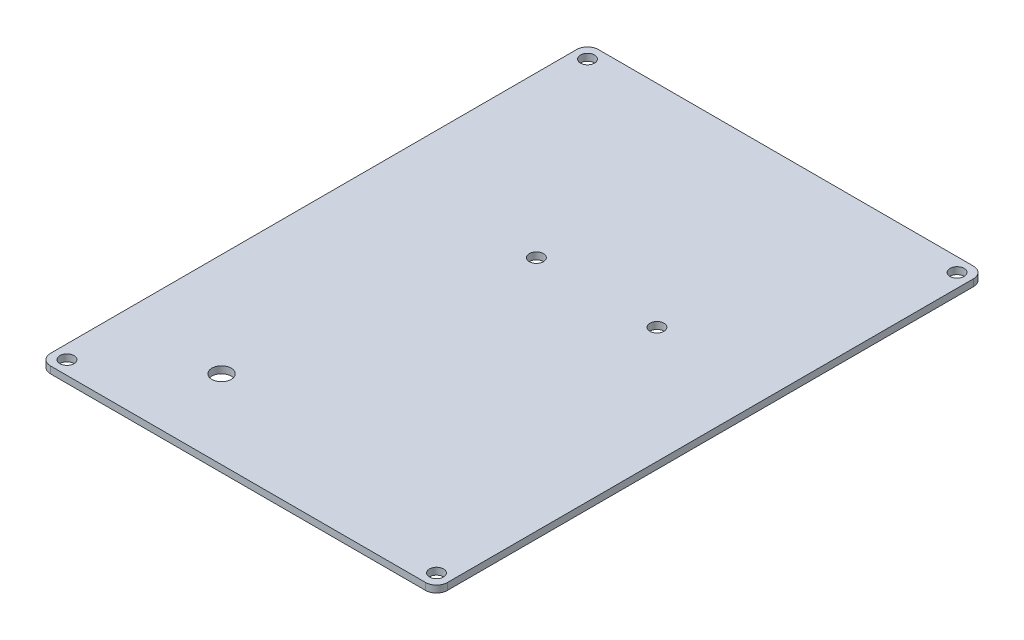
SolidWorks part; units mm, degrees
ref_plane "Front" through (0, 0, 0) normal (0, 0, 1) x (1, 0, 0)
ref_plane "Top" through (0, 0, 0) normal (0, 1, 0) x (1, 0, 0)
ref_plane "Right" through (0, 0, 0) normal (1, 0, 0) x (0, 0, -1)
sketch "Sketch1" plane through (0, 0, 0) normal (0, 1, 0) x (1, 0, 0)
  line L1 (-46, -63.5) -> (46, -63.5)
  line L2 (-46, -63.5) -> (-46, 63.5)
  line L3 (-46, 63.5) -> (46, 63.5)
  line L4 (46, -63.5) -> (46, 63.5)
  line L5 (-46, -63.5) -> (46, 63.5) construction
  line L6 (-46, 63.5) -> (46, -63.5) construction
  point P0 (0, 0)
  dimension "D1" = 127
  dimension "D2" = 92
extrude "Boss-Extrude1" add sketch "Sketch1" along normal blind 1.6
hole_wizard "#4 Clearance Hole2" positions "Sketch2" profile "Sketch3" hole size "#4" standard "ANSI Inch"
sketch "Sketch2" plane through (0, 1.6, 0) normal (0, 1, 0) x (1, 0, 0)
  line L1 (-42.825, 60.325) -> (42.825, 60.325)
  line L2 (-42.825, 60.325) -> (-42.825, -60.325)
  line L3 (-42.825, -60.325) -> (42.825, -60.325)
  line L4 (42.825, 60.325) -> (42.825, -60.325)
  line L5 (-42.825, 60.325) -> (42.825, -60.325) construction
  line L6 (-42.825, -60.325) -> (42.825, 60.325) construction
  line L9 (46, -63.5) -> (46, 63.5) construction
  line L10 (-46, -63.5) -> (46, -63.5) construction
  point P0 (-42.825, 60.325)
  point P2 (42.825, 60.325)
  point P4 (42.825, -60.325)
  point P6 (-42.825, -60.325)
  dimension "D1" = 3.175
  dimension "D2" = 3.175
sketch "Sketch3" plane through (-42.825, 1.6, -60.325) normal (1, 0, 0) x (0, 0, 1)
  line L0 (0, 0) -> (0, 50.9806)
  line L1 (0, 50.9806) -> (1.6319, 50)
  line L2 (1.6319, 50) -> (1.6319, 0)
  line L5 (1.6319, 0) -> (0, 0)
  line L10 (0, 50.9806) -> (-1.632, 50) construction
  line L11 (0, -6.35) -> (0, 107.95) construction
  dimension "Hole Dia." = 3.2639
  dimension "Hole Depth" = 50
  dimension "Drill Angle" = 118
fillet "Fillet1" radius 2.54 4 edges at (46, 0.8, 63.5) (46, 0.8, -63.5) (-46, 0.8, -63.5) (-46, 0.8, 63.5)
hole_wizard "#4 Clearance Hole1" positions "Sketch4" profile "Sketch5" hole size "#4" standard "ANSI Inch"
sketch "Sketch4" plane through (0, 1.6, 0) normal (0, 1, 0) x (1, 0, 0)
  line L1 (46, -60.96) -> (46, 60.96) construction
  line L2 (43.46, 63.5) -> (-43.46, 63.5) construction
  line L3 (-46, 60.96) -> (-46, -60.96) construction
  point P22 (19.05, 14.54)
  point P24 (-8.89, 14.54)
  dimension "D1" = 26.95
  dimension "D2" = 48.96
  dimension "D3" = 48.96
  dimension "D4" = 37.11
sketch "Sketch5" plane through (19.05, 1.6, -14.54) normal (1, 0, 0) x (0, 0, 1)
  line L0 (0, 0) -> (0, 19.7306)
  line L1 (0, 19.7306) -> (1.6319, 18.75)
  line L2 (1.6319, 18.75) -> (1.6319, 0)
  line L5 (1.6319, 0) -> (0, 0)
  line L10 (0, 19.7306) -> (-1.632, 18.75) construction
  line L11 (0, -6.35) -> (0, 107.95) construction
  dimension "Hole Dia." = 3.2639
  dimension "Hole Depth" = 18.75
  dimension "Drill Angle" = 118
hole_wizard "#8 Clearance Hole1" positions "Sketch6" profile "Sketch7" hole size "#8" standard "ANSI Inch"
sketch "Sketch6" plane through (0, 0, 0) normal (0, -1, 0) x (-1, 0, 0)
  circle A0 centre (22.07, -45.25) radius 1.5 construction
  point P0 (22.07, -45.25)
sketch "Sketch7" plane through (-22.07, 0, 45.25) normal (1, 0, 0) x (0, 0, -1)
  line L0 (0, 0) -> (0, 20.1007)
  line L1 (0, 20.1007) -> (2.2479, 18.75)
  line L2 (2.2479, 18.75) -> (2.2479, 0)
  line L5 (2.2479, 0) -> (0, 0)
  line L10 (0, 20.1007) -> (-2.2479, 18.75) construction
  line L11 (0, -6.35) -> (0, 107.95) construction
  dimension "Hole Dia." = 4.4958
  dimension "Hole Depth" = 18.75
  dimension "Drill Angle" = 118
ref_point "PCB_ORIGIN"
sketch "TOP_KEEPOUT" plane through (0, 1.6, 0) normal (0, 1, 0) x (1, 0, 0)
  circle A0 centre (-8.89, 14.54) radius 3.429
  circle A1 centre (19.05, 14.54) radius 3.429
  circle A2 centre (42.825, 60.325) radius 3.429
  circle A3 centre (-42.825, 60.325) radius 3.429
  circle A4 centre (42.825, -60.325) radius 3.429
  circle A5 centre (-42.825, -60.325) radius 3.429
  dimension "D1" = 6.858
sketch "BOTTOM_KEEPOUT" plane through (0, 0, 0) normal (0, -1, 0) x (1, 0, 0)
  line L0 (-26.67, -46.036) -> (-26.67, -3.11) construction
  line L1 (26.67, -47.56) -> (-26.67, -47.56)
  line L2 (26.67, -47.56) -> (26.67, 51.5)
  line L3 (26.67, 51.5) -> (-21.67, 51.5)
  line L4 (-26.67, -47.56) -> (-26.67, 41.5)
  line L7 (-13.716, -47.56) -> (-25.146, -47.56) construction
  line L9 (26.67, -3.11) -> (26.67, -46.56) construction
  line L10 (-25.67, 51.5) -> (25.67, 51.5) construction
  line L11 (-21.67, 51.5) -> (-21.67, 41.5)
  line L12 (-21.67, 41.5) -> (-26.67, 41.5)
  circle A0 centre (-42.825, 60.325) radius 3.937
  circle A1 centre (42.825, 60.325) radius 3.937
  circle A2 centre (42.825, -60.325) radius 3.937
  circle A3 centre (-42.825, -60.325) radius 3.937
  dimension "D1" = 7.874
  dimension "D4" = 5
  dimension "D5" = 10
sketch "TOP_CONN_POS" plane through (0, 1.6, 0) normal (0, 1, 0) x (1, 0, 0)
  line L0 (6.35, -35.308) -> (6.35, -45.308)
  line L1 (-37.936, 28.7076) -> (-37.936, 18.7076)
  line L2 (1.35, -40.308) -> (11.35, -40.308)
  line L3 (-42.936, 23.7076) -> (-32.936, 23.7076)
  line L4 (0, 60.436) -> (0, 50.436)
  line L5 (-5, 55.436) -> (5, 55.436)
  line L6 (-37.936, -5.35) -> (-37.936, 52.7652) construction
  line L7 (-43.524, 23.7076) -> (-32.348, 23.7076) construction
  line L8 (0, 61.024) -> (0, 49.848) construction
  line L9 (-29.0576, 55.436) -> (29.0576, 55.436) construction
  line L10 (37.936, 28.7076) -> (37.936, 18.7076)
  line L11 (32.936, 23.7076) -> (42.936, 23.7076)
  line L12 (43.524, 23.7076) -> (32.348, 23.7076) construction
  line L13 (37.936, 52.7652) -> (37.936, -5.35) construction
  line L14 (37.936, -25.0576) -> (37.936, -35.0576)
  line L15 (32.936, -30.0576) -> (42.936, -30.0576)
  line L16 (37.936, -52.7652) -> (37.936, -7.35) construction
  line L17 (43.524, -30.0576) -> (32.348, -30.0576) construction
  line L18 (0, -50.436) -> (0, -60.436)
  line L19 (-5, -55.436) -> (5, -55.436)
  line L20 (29.0576, -55.436) -> (-29.0576, -55.436) construction
  line L21 (0, -61.024) -> (0, -49.848) construction
  line L22 (6.35, -45.896) -> (6.35, -34.72) construction
  line L23 (-16.3576, -40.308) -> (29.0576, -40.308) construction
  point P2 (6.35, -40.308)
  point P9 (-37.936, 23.7076)
  point P14 (0, 55.436)
  point P29 (37.936, 23.7076)
  point P40 (37.936, -30.0576)
  point P50 (0, -55.436)
  dimension "D1" = 10
  dimension "D2" = 0
  dimension "D3" = 0
  dimension "D4" = 0
  dimension "D5" = 0
  dimension "D6" = 0
  dimension "D7" = 0
  dimension "D8" = 0
  dimension "D9" = 0
  dimension "D10" = 0
  dimension "D11" = 0
  dimension "D12" = 0
  dimension "D13" = 0
sketch "BOTTOM_CONN_POS" plane through (0, 1.6, 0) normal (0, 1, 0) x (1, 0, 0)
  line L0 (0, 12.768) -> (0, -17.232)
  line L1 (-15, -2.232) -> (15, -2.232)
  line L2 (-41.4, 47.425) -> (-41.4, 37.425)
  line L3 (-46.4, 42.425) -> (-36.4, 42.425)
  line L4 (-46, 42.425) -> (-30.6, 42.425) construction
  line L5 (-41.4, 50.75) -> (-41.4, 34.1) construction
  line L6 (-41.4, 28.775) -> (-41.4, 18.775)
  line L7 (-46.4, 23.775) -> (-36.4, 23.775)
  line L8 (-41.4, 13.125) -> (-41.4, 3.125)
  line L9 (-46.4, 8.125) -> (-36.4, 8.125)
  line L10 (-41.4, 0.475) -> (-41.4, -9.525)
  line L11 (-46.4, -4.525) -> (-36.4, -4.525)
  line L12 (-41.4, -12.175) -> (-41.4, -22.175)
  line L13 (-46.4, -17.175) -> (-36.4, -17.175)
  line L14 (-46, 23.775) -> (-30.6, 23.775) construction
  line L15 (-46, 8.125) -> (-30.6, 8.125) construction
  line L16 (-46, -4.525) -> (-30.6, -4.525) construction
  line L17 (-46, -17.175) -> (-30.6, -17.175) construction
  line L18 (-39, -24.8) -> (-39, -34.8)
  line L19 (-44, -29.8) -> (-34, -29.8)
  line L20 (-41.4, -38.925) -> (-41.4, -48.925)
  line L21 (-46.4, -43.925) -> (-36.4, -43.925)
  line L22 (-27.925, -53.9) -> (-27.925, -63.9)
  line L24 (-32.925, -58.9) -> (-22.925, -58.9)
  line L26 (29.425, -53.9) -> (29.425, -63.9)
  line L27 (24.425, -58.9) -> (34.425, -58.9)
  line L28 (29.425, -53.9) -> (29.425, -63.9)
  line L29 (24.425, -58.9) -> (34.425, -58.9)
  line L30 (29.425, -53.9) -> (29.425, -63.9)
  line L31 (24.425, -58.9) -> (34.425, -58.9)
  line L32 (-39, -34.5) -> (-39, -25.1) construction
  line L33 (-42.65, -29.8) -> (-35.5, -29.8) construction
  line L34 (-46, -43.925) -> (-30.92, -43.925) construction
  line L35 (-41.4, -50.75) -> (-41.4, -37.1) construction
  line L36 (-21.1, -58.9) -> (-34.75, -58.9) construction
  line L37 (-27.925, -63.5) -> (-27.925, -48.42) construction
  line L38 (34.75, -58.9) -> (24.1, -58.9) construction
  line L39 (29.425, -63.5) -> (29.425, -48.1) construction
  line L40 (39.35, -41.4) -> (39.35, -51.4)
  line L41 (34.35, -46.4) -> (44.35, -46.4)
  line L42 (41.4, -9.175) -> (41.4, -19.175)
  line L43 (36.4, -14.175) -> (46.4, -14.175)
  line L44 (39.35, -24.3) -> (39.35, -34.3)
  line L45 (34.35, -29.3) -> (44.35, -29.3)
  line L46 (39.35, -39.2) -> (39.35, -53.6) construction
  line L47 (35.85, -46.4) -> (43, -46.4) construction
  line L48 (35.85, -29.3) -> (43, -29.3) construction
  line L49 (41.4, -8.85) -> (41.4, -19.5) construction
  line L50 (46, -14.175) -> (30.6, -14.175) construction
  line L51 (41.4, 3.475) -> (41.4, -6.525)
  line L52 (36.4, -1.525) -> (46.4, -1.525)
  line L53 (41.4, 17.625) -> (41.4, 7.625)
  line L54 (36.4, 12.625) -> (46.4, 12.625)
  line L61 (46, -1.525) -> (30.6, -1.525) construction
  line L62 (46, 12.625) -> (30.92, 12.625) construction
  line L63 (41.4, 33.275) -> (41.4, 23.275)
  line L64 (36.4, 28.275) -> (46.4, 28.275)
  line L65 (46, 28.275) -> (30.92, 28.275) construction
  line L66 (41.4, 48.925) -> (41.4, 38.925)
  line L67 (36.4, 43.925) -> (46.4, 43.925)
  line L68 (46, 43.925) -> (30.92, 43.925) construction
  line L69 (27.975, 63.9) -> (27.975, 53.9)
  line L70 (22.975, 58.9) -> (32.975, 58.9)
  line L71 (21.15, 58.9) -> (34.8, 58.9) construction
  line L72 (27.975, 63.5) -> (27.975, 48.42) construction
  line L73 (10.825, 63.9) -> (10.825, 53.9)
  line L74 (5.825, 58.9) -> (15.825, 58.9)
  line L75 (10.825, 63.5) -> (10.825, 48.1) construction
  line L76 (-7.825, 63.9) -> (-7.825, 53.9)
  line L77 (-12.825, 58.9) -> (-2.825, 58.9)
  line L78 (-7.825, 63.5) -> (-7.825, 48.1) construction
  line L79 (-26.475, 63.9) -> (-26.475, 53.9)
  line L80 (-31.475, 58.9) -> (-21.475, 58.9)
  line L81 (-26.475, 63.5) -> (-26.475, 48.1) construction
  line L82 (0, -51.5) -> (0, 50.1) construction
  line L83 (26.67, -2.232) -> (-26.67, -2.232) construction
  point P4 (0, -2.232)
  point P13 (-41.4, 42.425)
  point P24 (-41.4, 23.775)
  point P29 (-41.4, 8.125)
  point P34 (-41.4, -4.525)
  point P39 (-41.4, -17.175)
  point P56 (-39, -29.8)
  point P62 (-41.4, -43.925)
  point P68 (-27.925, -58.9)
  point P75 (29.425, -58.9)
  point P80 (29.425, -58.9)
  point P85 (29.425, -58.9)
  point P100 (29.425, -55.8)
  point P105 (39.35, -46.4)
  point P110 (41.4, -14.175)
  point P115 (39.35, -29.3)
  point P135 (41.4, -1.525)
  point P140 (41.4, 12.625)
  point P151 (41.4, 28.275)
  point P161 (41.4, 43.925)
  point P169 (27.975, 58.9)
  point P179 (10.825, 58.9)
  point P188 (-7.825, 58.9)
  point P197 (-26.475, 58.9)
  dimension "D1" = 30
  dimension "D2" = 10
  dimension "D3" = 0
  dimension "D4" = 0
  dimension "D5" = 10
  dimension "D6" = 10
  dimension "D7" = 10
  dimension "D8" = 10
  dimension "D9" = 0
  dimension "D10" = 0
  dimension "D11" = 0
  dimension "D12" = 0
  dimension "D13" = 10
  dimension "D14" = 10
  dimension "D15" = 10
  dimension "D16" = 0
  dimension "D17" = 0
  dimension "D18" = 0
  dimension "D19" = 0
  dimension "D20" = 0
  dimension "D21" = 0
  dimension "D22" = 0
  dimension "D23" = 0
  dimension "D24" = 0
  dimension "D25" = 0
  dimension "D26" = 0
  dimension "D27" = 0
  dimension "D28" = 0
  dimension "D29" = 10
  dimension "D30" = 10
  dimension "D31" = 0
  dimension "D32" = 0
  dimension "D33" = 10
  dimension "D34" = 0
  dimension "D35" = 10
  dimension "D36" = 0
  dimension "D37" = 10
  dimension "D38" = 0
  dimension "D39" = 0
  dimension "D40" = 10
  dimension "D41" = 0
  dimension "D42" = 10
  dimension "D43" = 0
  dimension "D44" = 10
  dimension "D45" = 0
  dimension "D46" = 0
  dimension "D47" = 0
